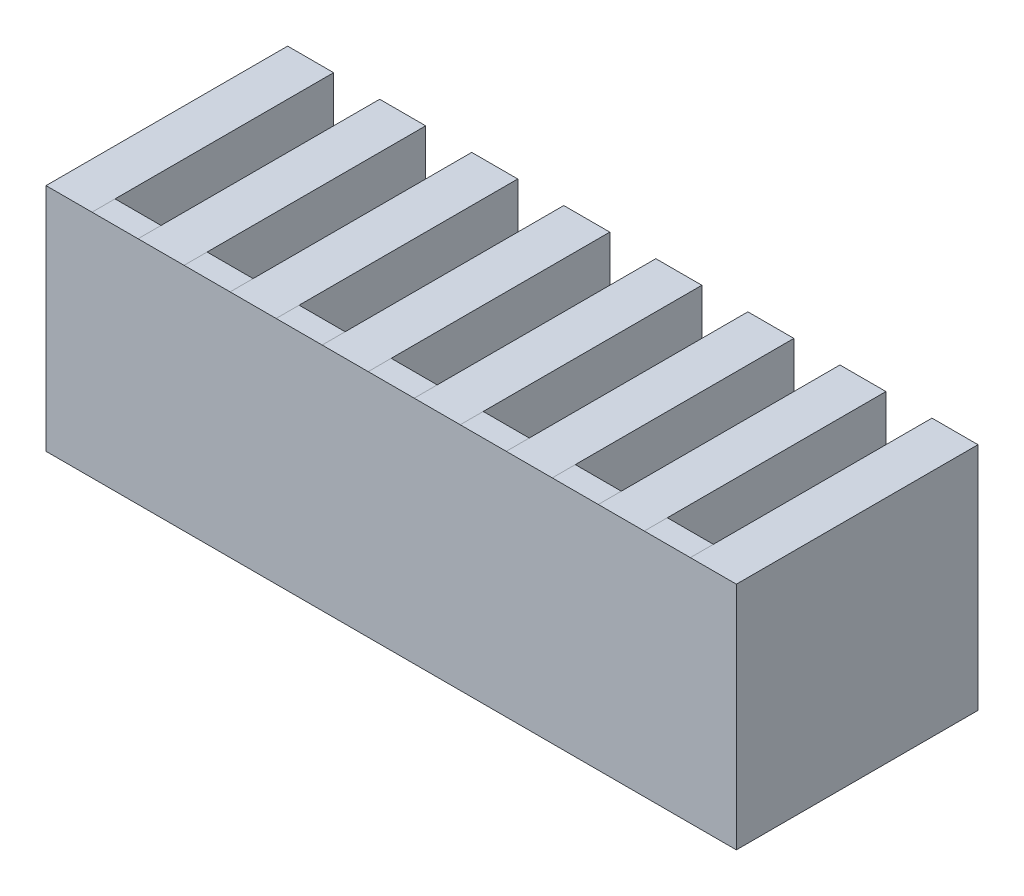
SolidWorks part; units mm, degrees
ref_plane "Front Plane" through (0, 0, 0) normal (0, 0, 1) x (1, 0, 0)
ref_plane "Top Plane" through (0, 0, 0) normal (0, 1, 0) x (1, 0, 0)
ref_plane "Right Plane" through (0, 0, 0) normal (1, 0, 0) x (0, 0, -1)
sketch "Sketch1" plane through (0, 0, 0) normal (0, 0, 1) x (1, 0, 0)
  line L1 (0, 0) -> (30, 0)
  line L2 (0, 0) -> (0, 10)
  line L3 (0, 10) -> (30, 10)
  line L4 (30, 0) -> (30, 10)
  dimension "D1" = 30
  dimension "D2" = 10
extrude "Boss-Extrude1" add sketch "Sketch1" along normal blind 10.5
sketch "Sketch3" plane through (0, 0, 0) normal (0, -1, 0) x (1, 0, 0)
  line L0 (0, 0) -> (30, 0) construction
  line L2 (2, 0) -> (2, 9.5)
  line L3 (2, 9.5) -> (4, 9.5)
  line L4 (4, 0) -> (4, 9.5)
  line L5 (0, 10.5) -> (0, 0) construction
  dimension "D1" = 2
  dimension "D2" = 2
  dimension "D3" = 9.5
extrude "Cut-Extrude1" cut sketch "Sketch3" against normal through all and the other way through all
pattern_linear "LPattern1" count 13 spacing 2 along (1, 0, 0) skipping (1, 0), (3, 0), (5, 0), (7, 0), (9, 0), (11, 0) of "Cut-Extrude1"
sketch "Sketch4" plane through (0, 0, 0) normal (0, -1, 0) x (1, 0, 0)
  line L0 (2, 9.5) -> (2, 10.5)
  line L1 (0, 10.5) -> (30, 10.5) construction
  line L2 (4, 9.5) -> (4, 10.5)
  line L3 (6, 9.5) -> (6, 10.5)
  line L4 (8, 9.5) -> (8, 10.5)
  line L5 (10, 9.5) -> (10, 10.5)
  line L6 (12, 9.5) -> (12, 10.5)
  line L7 (14, 9.5) -> (14, 10.5)
  line L8 (16, 9.5) -> (16, 10.5)
  line L9 (18, 9.5) -> (18, 10.5)
  line L10 (20, 9.5) -> (20, 10.5)
  line L11 (22, 9.5) -> (22, 10.5)
  line L12 (24, 9.5) -> (24, 10.5)
  line L13 (26, 9.5) -> (26, 10.5)
  line L14 (28, 9.5) -> (28, 10.5)
  dimension "D1" = 14
split line "Split Line1"
sketch "Sketch5" plane through (0, 10, 0) normal (0, 1, 0) x (1, 0, 0)
  line L0 (28, -9.5) -> (28, -10.5)
  line L1 (30, -10.5) -> (0, -10.5) construction
  line L2 (26, -9.5) -> (26, -10.5)
  line L3 (24, -9.5) -> (24, -10.5)
  line L4 (22, -9.5) -> (22, -10.5)
  line L5 (20, -9.5) -> (20, -10.5)
  line L6 (18, -9.5) -> (18, -10.5)
  line L7 (16, -9.5) -> (16, -10.5)
  line L8 (14, -9.5) -> (14, -10.5)
  line L9 (12, -9.5) -> (12, -10.5)
  line L10 (10, -9.5) -> (10, -10.5)
  line L11 (8, -9.5) -> (8, -10.5)
  line L12 (6, -9.5) -> (6, -10.5)
  line L13 (4, -9.5) -> (4, -10.5)
  line L14 (2, -9.5) -> (2, -10.5)
  dimension "D1" = 14
split line "Split Line2"
